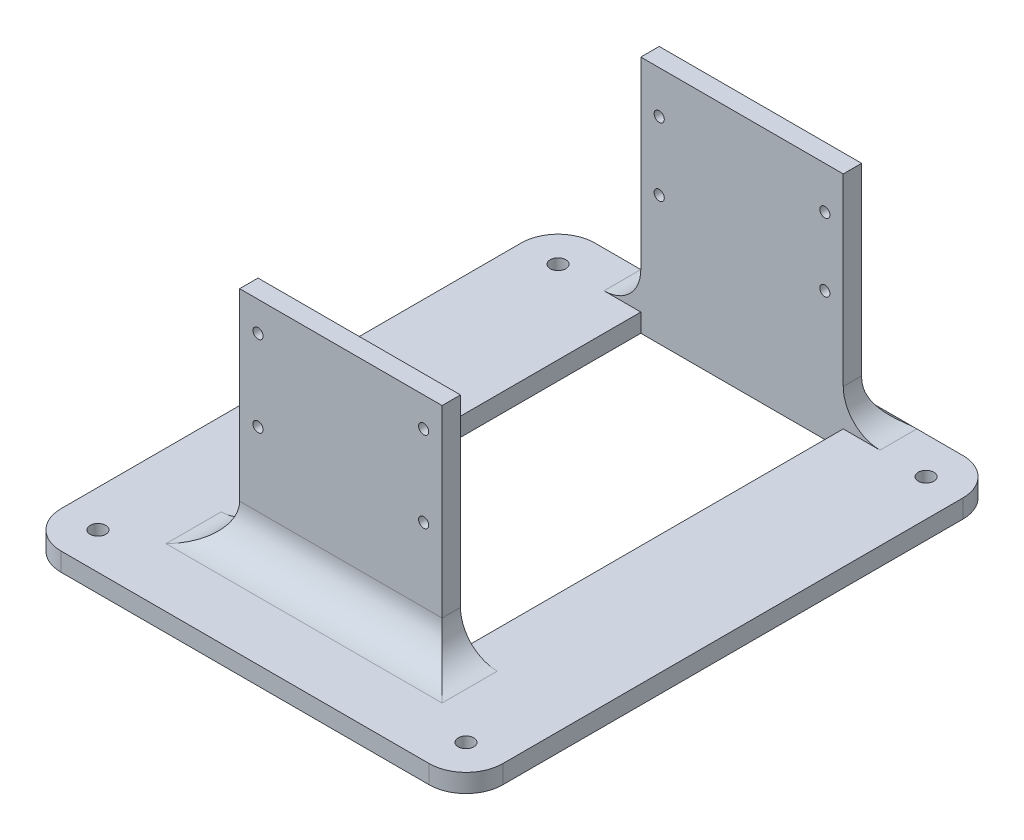
SolidWorks part; units mm, degrees
other "Markup1"
sketch "Sketch7" plane through (-69.5, 3, -80) normal (0, 1, 0) x (1, 0, 0)
sketch "Sketch8" plane through (-69.5, 5, -80) normal (0, 1, 0) x (1, 0, 0)
other "Markup2"
sketch "Sketch17" plane through (60, 65, 65) normal (0.6864, 0.6858, 0.2418) x (0.2362, 0.1043, -0.9661)
ref_plane "Front Plane" through (0, 0, 0) normal (0, 0, 1) x (1, 0, 0)
ref_plane "Top Plane" through (0, 0, 0) normal (0, 1, 0) x (1, 0, 0)
ref_plane "Right Plane" through (0, 0, 0) normal (1, 0, 0) x (0, 0, -1)
sketch "Sketch1" plane through (0, 0, 0) normal (0, 1, 0) x (1, 0, 0)
  line L1 (-60, 65) -> (60, 65)
  line L2 (-60, 65) -> (-60, -65)
  line L3 (-60, -65) -> (60, -65)
  line L4 (60, 65) -> (60, -65)
  line L5 (-60, 65) -> (60, -65) construction
  line L6 (-60, -65) -> (60, 65) construction
  point P0 (0, 0)
  dimension "D1" = 130
  dimension "D2" = 120
extrude "Boss-Extrude1" add sketch "Sketch1" along normal blind 5
sketch "Sketch10" plane through (0, 5, 0) normal (0, 1, 0) x (1, 0, 0)
  line L0 (-60, 65) -> (60, 65)
  line L1 (-60, 65) -> (-60, 80)
  line L2 (60, 65) -> (60, 80)
  line L3 (-60, 80) -> (60, 80)
  line L4 (60, 65) -> (-60, 65) construction
  line L5 (-60, 65) -> (-60, -65) construction
  line L6 (60, -65) -> (60, 65) construction
  dimension "D1" = 0
  dimension "D2" = 0
  dimension "D3" = 15
extrude "Boss-Extrude2" add sketch "Sketch10" against normal up to surface (5 mm away) up to face at (0, 0, 0)
sketch "Sketch9" plane through (0, 5, 0) normal (0, 1, 0) x (1, 0, 0)
  line L0 (0, -55) -> (0, 55) construction
  line L1 (-27.5, -34) -> (27.5, -34)
  line L2 (-27.5, -34) -> (-27.5, 70)
  line L3 (-27.5, 70) -> (27.5, 70)
  line L4 (27.5, -34) -> (27.5, 70)
  line L5 (-27.5, -34) -> (27.5, 70) construction
  line L6 (-27.5, 70) -> (27.5, -34) construction
  line L8 (60, 80) -> (-60, 80) construction
  point P0 (0, 18)
  dimension "D1" = 10
  dimension "D2" = 104
  dimension "D3" = 55
extrude "Cut-Extrude5" cut sketch "Sketch9" against normal through all
sketch "Sketch11" plane through (0, 5, 0) normal (0, 1, 0) x (1, 0, 0)
  line L0 (-27.5, 70) -> (27.5, 70)
  line L1 (-27.5, 70) -> (-27.5, 75)
  line L2 (27.5, 70) -> (27.5, 75)
  line L3 (-27.5, 75) -> (27.5, 75)
  line L4 (-27.5, -34) -> (27.5, -34)
  line L5 (-27.5, -34) -> (-27.5, -39)
  line L6 (27.5, -34) -> (27.5, -39)
  line L7 (-27.5, -39) -> (27.5, -39)
  dimension "D1" = 5
  dimension "D2" = 5
extrude "Boss-Extrude3" add sketch "Sketch11" along normal blind 60
sketch "Sketch12" plane through (0, 0, 39) normal (0, 0, 1) x (1, 0, 0)
  line L0 (-27.5, 5) -> (27.5, 5) construction
  line L1 (0, -55) -> (0, 55) construction
  circle A0 centre (-22.5, 35) radius 1.375
  circle A2 centre (22.5, 35) radius 1.375
  dimension "D3" = 2.75
  dimension "D1" = 30
  dimension "D2" = 22.5
extrude "Cut-Extrude6" cut sketch "Sketch12" against normal through all
sketch "Sketch13" plane through (0, 0, 39) normal (0, 0, 1) x (1, 0, 0)
  line L0 (0, -55) -> (0, 55) construction
  circle A0 centre (-22.5, 57) radius 1.375
  circle A1 centre (-22.5, 35) radius 1.375 construction
  circle A2 centre (22.5, 57) radius 1.375
  dimension "D2" = 2.75
  dimension "D1" = 22.5
  dimension "D3" = 22
extrude "Cut-Extrude7" cut sketch "Sketch13" against normal up to next
sketch "Sketch14" plane through (0, 0, -75) normal (0, 0, -1) x (-1, 0, 0)
  line L0 (-22.5, 35) -> (-22.5, 57.1524) construction
  line L1 (0, 55) -> (0, -55) construction
  circle A0 centre (-22.5, 53.5) radius 1.375
  circle A1 centre (22.5, 53.5) radius 1.375
  dimension "D2" = 2.75
  dimension "D1" = 18.5
extrude "Cut-Extrude8" cut sketch "Sketch14" against normal up to next
fillet "Fillet1" radius 10 1 edges at (0, 5, 39)
fillet "Fillet2" radius 10 1 edges at (0, 5, -75)
fillet "Fillet3" radius 10 4 edges at (27.5, 5, -75) (27.5, 5, 41.5) (-27.5, 5, 41.5) (-27.5, 5, -75)
sketch "Sketch16" plane through (0, 5, 0) normal (0, 1, 0) x (1, 0, 0)
  line L0 (-37.5, 80) -> (-60, 80) construction
  line L1 (-60, 80) -> (-60, -65) construction
  line L2 (-60, -65) -> (60, -65) construction
  line L3 (60, -65) -> (60, 80) construction
  circle A0 centre (-50, 70) radius 2.125
  circle A1 centre (-50, -55) radius 2.125
  circle A2 centre (50, -55) radius 2.125
  circle A3 centre (50, 70) radius 2.125
  dimension "D1" = 4.25
  dimension "D2" = 4.25
  dimension "D3" = 4.25
  dimension "D4" = 4.25
  dimension "D5" = 10
  dimension "D6" = 10
  dimension "D7" = 10
  dimension "D8" = 10
extrude "Cut-Extrude9" cut sketch "Sketch16" against normal blind 10
fillet "Fillet4" radius 10 4 edges at (-60, 2.5, -80) (60, 2.5, -80) (-60, 2.5, 65) (60, 2.5, 65)
